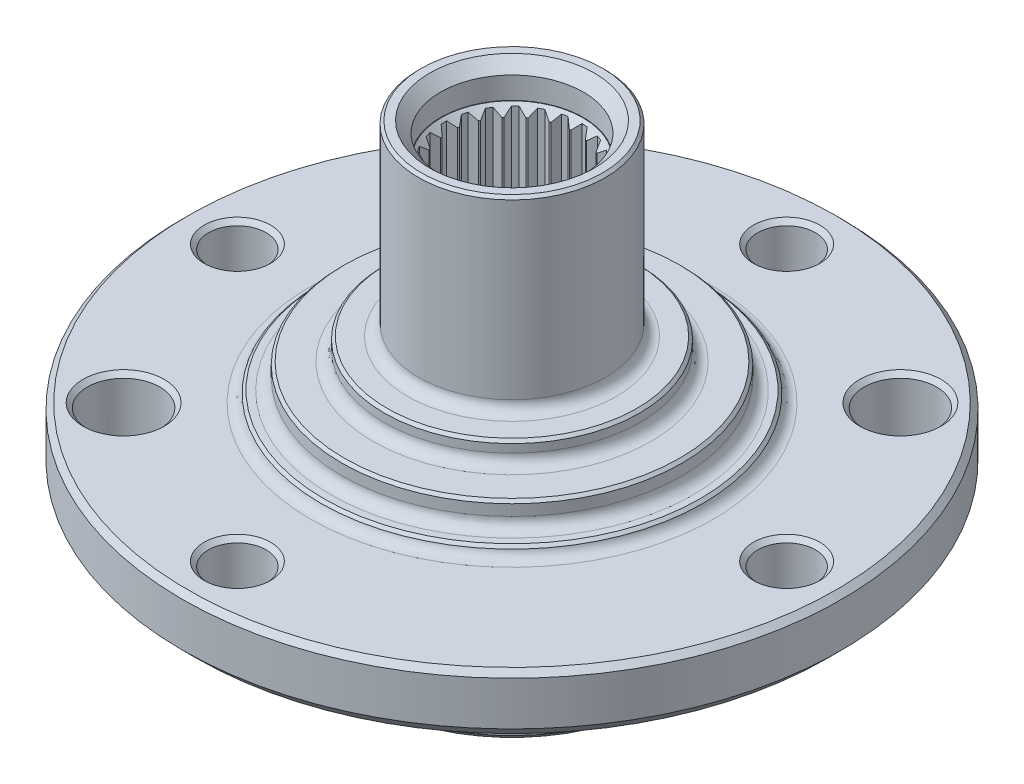
SolidWorks part; units mm, degrees
ref_plane "Plano frontal" through (0, 0, 0) normal (0, 0, 1) x (1, 0, 0)
ref_plane "Plano superior" through (0, 0, 0) normal (0, 1, 0) x (1, 0, 0)
ref_plane "Plano direito" through (0, 0, 0) normal (1, 0, 0) x (0, 0, -1)
sketch "Esboço1" plane through (0, 0, 0) normal (0, 0, 1) x (1, 0, 0)
  line L0 (0, 54.7476) -> (0, -54.9684) construction
  line L1 (13, 44.5) -> (13, 38.5)
  line L2 (23.5, -33.5) -> (28.25, -33.5)
  line L3 (28.25, -33.5) -> (28.25, -11.5)
  line L4 (28.25, -11.5) -> (60, -11.5)
  line L5 (13, 38.5) -> (11.4, 38.5)
  line L6 (11.4, 38.5) -> (11.4, -15.5)
  line L7 (60, -11.5) -> (60, 0)
  line L8 (60, 0) -> (34.75, 0)
  line L9 (34.75, 0) -> (34.75, 2)
  line L10 (34.75, 2) -> (31, 2)
  line L11 (31, 2) -> (31, 6.5)
  line L12 (31, 6.5) -> (23.25, 6.5)
  line L13 (23.25, 6.5) -> (23.25, 10.5)
  line L14 (23.25, 10.5) -> (17, 10.5)
  line L15 (17, 10.5) -> (17, 44.5)
  line L16 (17, 44.5) -> (13, 44.5)
  line L17 (11.4, -15.5) -> (23.5, -15.5)
  line L18 (23.5, -15.5) -> (23.5, -33.5)
  dimension "D1" = 22
  dimension "D2" = 18
  dimension "D3" = 34
  dimension "D4" = 38
  dimension "D5" = 42.5
  dimension "D6" = 44.5
  dimension "D7" = 11.5
  dimension "D8" = 13
  dimension "D9" = 17
  dimension "D10" = 23.5
  dimension "D11" = 28.25
  dimension "D12" = 23.25
  dimension "D13" = 34.75
  dimension "D14" = 31
  dimension "D15" = 60
  dimension "D16" = 11.4
  dimension "D17" = 6
revolve "Revolução1" add sketch "Esboço1" angle 360 about L0
chamfer "Chanfro10" distance 1.5 angle 45 1 edges at (0, 38.5, 11.4)
chamfer "Chanfro11" distance 1.5 angle 45 1 edges at (0, -15.5, 11.4)
sketch "Esboço4" plane through (0, -15.5, 0) normal (0, -1, 0) x (1, 0, 0)
  line L0 (-12.4, 0.5) -> (-12.4, 0)
  line L1 (0, 0) -> (-12.4, 0) construction
  line L2 (-12.4, 0) -> (-12.4, -0.5)
  line L3 (-11.8053, 3.8269) -> (-11.9402, 3.3455)
  line L4 (-11.9402, 3.3455) -> (-12.0751, 2.864)
  line L5 (-11.8053, 3.8269) -> (-10.5165, 4.4005)
  line L6 (-12.4, 0.5) -> (-11.3137, 1.4)
  line L7 (-11.3137, 1.4) -> (-11.3137, -1.4)
  line L8 (-12.4, -0.5) -> (-11.3137, -1.4)
  line L9 (-10.5165, 4.4005) -> (-11.2719, 1.7043)
  line L10 (-12.0751, 2.864) -> (-11.2719, 1.7043)
  line L11 (-10.335, 6.8701) -> (-10.5948, 6.4428)
  line L12 (-10.5948, 6.4428) -> (-10.8546, 6.0156)
  line L13 (-10.335, 6.8701) -> (-8.9392, 7.0746)
  line L14 (-8.9392, 7.0746) -> (-10.3941, 4.6822)
  line L15 (-10.8546, 6.0156) -> (-10.3941, 4.6822)
  line L16 (-8.0982, 9.4036) -> (-8.4637, 9.0624)
  line L17 (-8.4637, 9.0624) -> (-8.8291, 8.7211)
  line L18 (-8.0982, 9.4036) -> (-6.699, 9.224)
  line L19 (-6.699, 9.224) -> (-8.7454, 7.3129)
  line L20 (-8.8291, 8.7211) -> (-8.7454, 7.3129)
  line L21 (-5.2609, 11.2398) -> (-5.7048, 11.0098)
  line L22 (-5.7048, 11.0098) -> (-6.1487, 10.7797)
  line L23 (-5.2609, 11.2398) -> (-3.962, 10.6894)
  line L24 (-3.962, 10.6894) -> (-6.4481, 9.4012)
  line L25 (-6.1487, 10.7797) -> (-6.4481, 9.4012)
  line L26 (-2.0333, 12.2424) -> (-2.5229, 12.1406)
  line L27 (-2.5229, 12.1406) -> (-3.0124, 12.0389)
  line L28 (-2.0333, 12.2424) -> (-0.9311, 11.3619)
  line L29 (-0.9311, 11.3619) -> (-3.6726, 10.7922)
  line L30 (-3.0124, 12.0389) -> (-3.6726, 10.7922)
  line L31 (1.345, 12.337) -> (0.8462, 12.3711)
  line L32 (0.8462, 12.3711) -> (0.3474, 12.4052)
  line L33 (1.345, 12.337) -> (2.1688, 11.1918)
  line L34 (2.1688, 11.1918) -> (-0.6247, 11.3829)
  line L35 (0.3474, 12.4052) -> (-0.6247, 11.3829)
  line L36 (4.6236, 11.5166) -> (4.1525, 11.684)
  line L37 (4.1525, 11.684) -> (3.6814, 11.8515)
  line L38 (4.6236, 11.5166) -> (5.1079, 10.1916)
  line L39 (5.1079, 10.1916) -> (2.4696, 11.1293)
  line L40 (3.6814, 11.8515) -> (2.4696, 11.1293)
  line L41 (7.5593, 9.8421) -> (7.1508, 10.1304)
  line L42 (7.1508, 10.1304) -> (6.7424, 10.4188)
  line L43 (7.5593, 9.8421) -> (7.6682, 8.4356)
  line L44 (7.6682, 8.4356) -> (5.3806, 10.0503)
  line L45 (6.7424, 10.4188) -> (5.3806, 10.0503)
  line L46 (9.9344, 7.4376) -> (9.6188, 7.8255)
  line L47 (9.6188, 7.8255) -> (9.3033, 8.2133)
  line L48 (9.9344, 7.4376) -> (9.6597, 6.0539)
  line L49 (9.6597, 6.0539) -> (7.8926, 8.2259)
  line L50 (9.3033, 8.2133) -> (7.8926, 8.2259)
  line L51 (11.5726, 4.4816) -> (11.3734, 4.9402)
  line L52 (11.3734, 4.9402) -> (11.1742, 5.3988)
  line L53 (11.5726, 4.4816) -> (10.9348, 3.2233)
  line L54 (10.9348, 3.2233) -> (9.8193, 5.7915)
  line L55 (11.1742, 5.3988) -> (9.8193, 5.7915)
  line L56 (12.3526, 1.1931) -> (12.2845, 1.6885)
  line L57 (12.2845, 1.6885) -> (12.2164, 2.1838)
  line L58 (12.3526, 1.1931) -> (11.399, 0.1536)
  line L59 (11.399, 0.1536) -> (11.0177, 2.9275)
  line L60 (12.2164, 2.1838) -> (11.0177, 2.9275)
  line L61 (12.2164, -2.1838) -> (12.2845, -1.6885)
  line L62 (12.2845, -1.6885) -> (12.3526, -1.1931)
  line L63 (12.2164, -2.1838) -> (11.0177, -2.9275)
  line L64 (11.0177, -2.9275) -> (11.399, -0.1536)
  line L65 (12.3526, -1.1931) -> (11.399, -0.1536)
  line L66 (11.1742, -5.3988) -> (11.3734, -4.9402)
  line L67 (11.3734, -4.9402) -> (11.5726, -4.4816)
  line L68 (11.1742, -5.3988) -> (9.8193, -5.7915)
  line L69 (9.8193, -5.7915) -> (10.9348, -3.2233)
  line L70 (11.5726, -4.4816) -> (10.9348, -3.2233)
  line L71 (9.3033, -8.2133) -> (9.6188, -7.8255)
  line L72 (9.6188, -7.8255) -> (9.9344, -7.4376)
  line L73 (9.3033, -8.2133) -> (7.8926, -8.2259)
  line L74 (7.8926, -8.2259) -> (9.6597, -6.0539)
  line L75 (9.9344, -7.4376) -> (9.6597, -6.0539)
  line L76 (6.7424, -10.4188) -> (7.1508, -10.1304)
  line L77 (7.1508, -10.1304) -> (7.5593, -9.8421)
  line L78 (6.7424, -10.4188) -> (5.3806, -10.0503)
  line L79 (5.3806, -10.0503) -> (7.6682, -8.4356)
  line L80 (7.5593, -9.8421) -> (7.6682, -8.4356)
  line L81 (3.6814, -11.8515) -> (4.1525, -11.684)
  line L82 (4.1525, -11.684) -> (4.6236, -11.5166)
  line L83 (3.6814, -11.8515) -> (2.4696, -11.1293)
  line L84 (2.4696, -11.1293) -> (5.1079, -10.1916)
  line L85 (4.6236, -11.5166) -> (5.1079, -10.1916)
  line L86 (0.3474, -12.4052) -> (0.8462, -12.3711)
  line L87 (0.8462, -12.3711) -> (1.345, -12.337)
  line L88 (0.3474, -12.4052) -> (-0.6247, -11.3829)
  line L89 (-0.6247, -11.3829) -> (2.1688, -11.1918)
  line L90 (1.345, -12.337) -> (2.1688, -11.1918)
  line L91 (-3.0124, -12.0389) -> (-2.5229, -12.1406)
  line L92 (-2.5229, -12.1406) -> (-2.0333, -12.2424)
  line L93 (-3.0124, -12.0389) -> (-3.6726, -10.7922)
  line L94 (-3.6726, -10.7922) -> (-0.9311, -11.3619)
  line L95 (-2.0333, -12.2424) -> (-0.9311, -11.3619)
  line L96 (-6.1487, -10.7797) -> (-5.7048, -11.0098)
  line L97 (-5.7048, -11.0098) -> (-5.2609, -11.2398)
  line L98 (-6.1487, -10.7797) -> (-6.4481, -9.4012)
  line L99 (-6.4481, -9.4012) -> (-3.962, -10.6894)
  line L100 (-5.2609, -11.2398) -> (-3.962, -10.6894)
  line L101 (-8.8291, -8.7211) -> (-8.4637, -9.0624)
  line L102 (-8.4637, -9.0624) -> (-8.0982, -9.4036)
  line L103 (-8.8291, -8.7211) -> (-8.7454, -7.3129)
  line L104 (-8.7454, -7.3129) -> (-6.699, -9.224)
  line L105 (-8.0982, -9.4036) -> (-6.699, -9.224)
  line L106 (-10.8546, -6.0156) -> (-10.5948, -6.4428)
  line L107 (-10.5948, -6.4428) -> (-10.335, -6.8701)
  line L108 (-10.8546, -6.0156) -> (-10.3941, -4.6822)
  line L109 (-10.3941, -4.6822) -> (-8.9392, -7.0746)
  line L110 (-10.335, -6.8701) -> (-8.9392, -7.0746)
  line L111 (-12.0751, -2.864) -> (-11.9402, -3.3455)
  line L112 (-11.9402, -3.3455) -> (-11.8053, -3.8269)
  line L113 (-12.0751, -2.864) -> (-11.2719, -1.7043)
  line L114 (-11.2719, -1.7043) -> (-10.5165, -4.4005)
  line L115 (-11.8053, -3.8269) -> (-10.5165, -4.4005)
  point P12 (-11.4, 0)
  point P15 (-10.9773, 3.0757)
  point P21 (-9.7404, 5.9233)
  point P27 (-7.7811, 8.3315)
  point P33 (-5.2447, 10.1219)
  point P39 (-2.3194, 11.1616)
  point P45 (0.778, 11.3734)
  point P51 (3.8176, 10.7418)
  point P57 (6.5742, 9.3135)
  point P63 (8.8431, 7.1944)
  point P69 (10.4562, 4.5418)
  point P75 (11.2938, 1.5523)
  point P81 (11.2938, -1.5523)
  point P87 (10.4562, -4.5418)
  point P93 (8.8431, -7.1944)
  point P99 (6.5742, -9.3135)
  point P105 (3.8176, -10.7418)
  point P111 (0.778, -11.3734)
  point P117 (-2.3194, -11.1616)
  point P123 (-5.2447, -10.1219)
  point P129 (-7.7811, -8.3315)
  point P135 (-9.7404, -5.9233)
  point P141 (-10.9773, -3.0757)
  dimension "D1" = 23
extrude "Corte-extrusão2" cut sketch "Esboço4" against normal through all
chamfer "Chanfro1" distance 1 angle 45 1 edges at (0, 0, 60)
chamfer "Chanfro2" distance 0.5 angle 45 3 edges at (0, 10.5, 23.25) (0, 6.5, 31) (0, 2, 34.75)
chamfer "Chanfro3" distance 0.5 angle 45 1 edges at (0, 44.5, 17)
chamfer "Chanfro4" distance 2 angle 45 1 edges at (0, 44.5, 13)
fillet "Filete1" radius 2 1 edges at (0, 10.5, 17)
chamfer "Chanfro6" distance 2.5 angle 45 1 edges at (0, -11.5, 60)
fillet "Filete2" radius 1.5 1 edges at (0, -11.5, 28.25)
chamfer "Chanfro7" distance 1 angle 45 2 edges at (0, -33.5, 23.5) (0, -33.5, 28.25)
fillet "Filete3" radius 1.5 1 edges at (0, -15.5, 23.5)
sketch "Esboço2" plane through (0, -11.5, 0) normal (0, -1, 0) x (1, 0, 0)
  circle A0 centre (0, 0) radius 50 construction
  circle A1 centre (0, 50) radius 5.25
  circle A2 centre (50, 0) radius 5.25
  circle A3 centre (0, -50) radius 5.25
  circle A4 centre (-50, 0) radius 5.25
  circle A8 centre (35.3553, -35.3553) radius 6.6
  circle A11 centre (-35.3553, -35.3553) radius 2.5
  circle A12 centre (-35.3553, 35.3553) radius 6.6
  circle A13 centre (0, 50) radius 6.6 [skipped]
  circle A14 centre (50, 0) radius 6.6 [skipped]
  circle A15 centre (-50, 0) radius 6.6 [skipped]
  circle A16 centre (0, -50) radius 6.6 [skipped]
  circle A17 centre (35.3553, 35.3553) radius 6.6 [skipped]
  circle A18 centre (-35.3553, -35.3553) radius 6.6 [skipped]
  dimension "D1" = 4
  dimension "D2" = 8
extrude "Corte-extrusão1" cut sketch "Esboço2" against normal through all
chamfer "Chanfro9" distance 0.8 angle 45 14 edges at (0, -11.5, 44.75) (0, 0, 44.75) (50, -11.5, -5.25) (50, 0, -5.25) (35.3553, -11.5, -41.9553) (35.3553, 0, -41.9553) (0, -11.5, -55.25) (0, 0, -55.25) (-35.3553, -11.5, -37.8553) (-35.3553, 0, -37.8553) (-50, 0, -5.25) (-50, -11.5, -5.25) (-35.3553, 0, 28.7553) (-35.3553, -11.5, 28.7553)
fillet "Filete4" radius 2 1 edges at (0, 0, 34.75)
fillet "Filete5" radius 2 2 edges at (0, 2, 31) (0, 6.5, 23.25)
